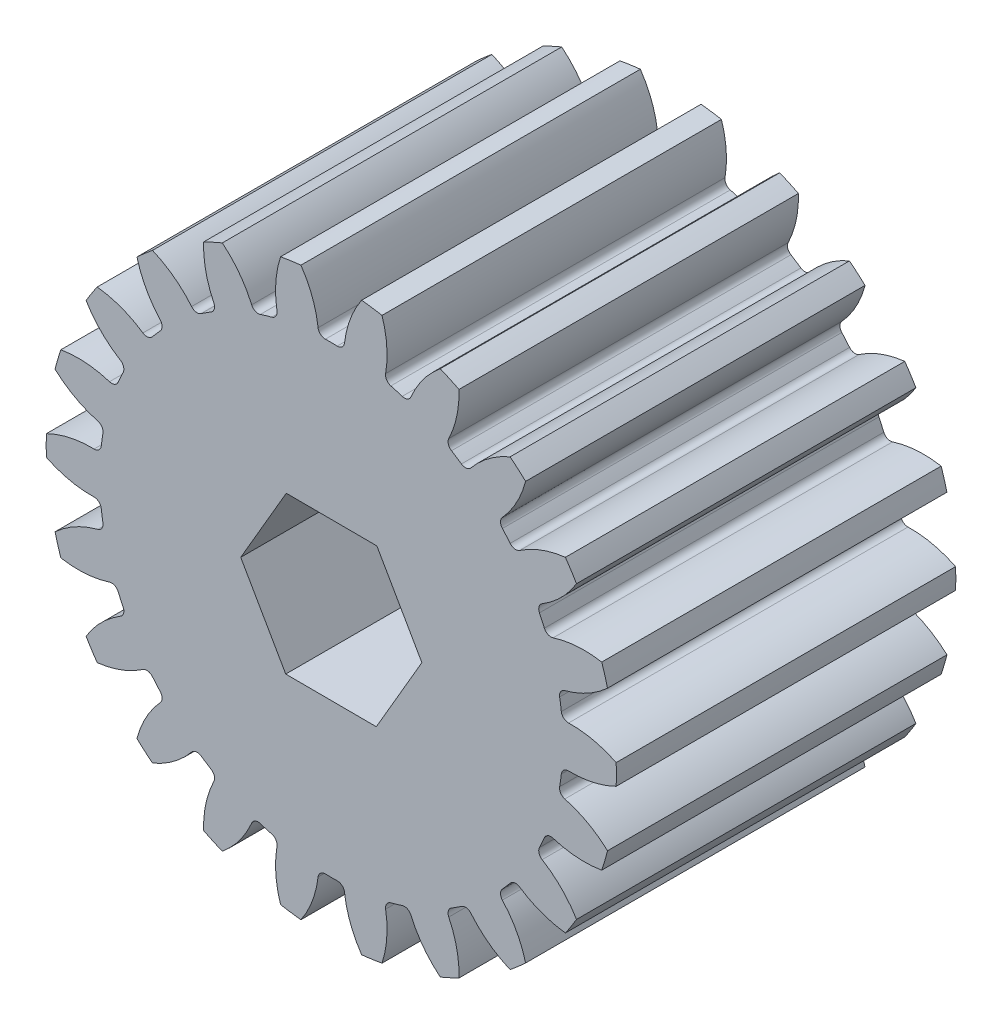
SolidWorks part; units mm, degrees
material "ABS"
ref_plane "Front Plane" through (0, 0, 0) normal (0, 0, 1) x (1, 0, 0)
ref_plane "Top Plane" through (0, 0, 0) normal (0, 1, 0) x (1, 0, 0)
ref_plane "Right Plane" through (0, 0, 0) normal (1, 0, 0) x (0, 0, -1)
sketch "Sketch1" plane through (0, 0, 0) normal (0, 0, 1) x (1, 0, 0)
  circle A0 centre (0, 0) radius 22
  circle A2 centre (0, 0) radius 24
  circle A3 centre (0, 0) radius 19.5
  dimension "D1" = 44
  dimension "D2" = 48
  dimension "D3" = 4.5
extrude "Boss-Extrude1" add sketch "Sketch1" along normal blind 25.4 and the other way blind 3.175 contours A2
sketch "Sketch3" plane through (0, 0, -3.175) normal (0, 0, -1) x (-1, 0, 0)
  line L0 (0, 0) -> (0, 24) construction
  line L1 (-1.5695, 21.9439) -> (1.5695, 21.9439) construction
  line L2 (0, 0) -> (-1.0635, 19.471) construction
  line L3 (0, 17.6319) -> (-2.6312, 24.8611) construction
  line L4 (0, 0) -> (3.4156, 23.7557) construction
  line L5 (1.5695, 21.9439) -> (4.6764, 21.4972) construction
  circle A0 centre (0, 0) radius 24 construction
  arc A1 (-3.2834, 24.7834) -> (-1.0635, 19.471) centre (-9.6529, 19.0018) cw
  arc A2 (3.2834, 24.7834) -> (1.0635, 19.471) centre (9.6529, 19.0018) ccw
  circle A3 centre (0, 0) radius 19.5 construction
  arc A4 (1.0635, 19.471) -> (-1.0635, 19.471) centre (0, 0) ccw
  arc A5 (3.2834, 24.7834) -> (-3.2834, 24.7834) centre (0, 0) ccw
  circle A6 centre (0, 0) radius 22 construction
  circle A8 centre (0, 0) radius 22 construction
  dimension "D2" = 20
  dimension "D3" = 8.182
extrude "Cut-Extrude2" cut sketch "Sketch3" against normal through all
fillet "Fillet2" radius 0.6 2 edges at (-1.0635, 19.471, 11.1125) (1.0635, 19.471, 11.1125)
pattern_circular "CirPattern2" count 22 over 360 about axis through (0, 0, -3.175) along (0, 0, 1) of "Cut-Extrude2", "Fillet2" reverse direction yes
sketch "Sketch4" plane through (0, 0, 25.4) normal (0, 0, 1) x (1, 0, 0)
  line L1 (3.8362, 6.5904) -> (-3.7894, 6.6175)
  line L2 (-3.7894, 6.6175) -> (-7.6256, 0.027)
  line L3 (-7.6256, 0.027) -> (-3.8362, -6.5904)
  line L4 (-3.8362, -6.5904) -> (3.7894, -6.6175)
  line L5 (3.7894, -6.6175) -> (7.6256, -0.027)
  line L6 (7.6256, -0.027) -> (3.8362, 6.5904)
  circle A0 centre (0, 0) radius 6.604 construction
  dimension "D1" = 13.208
extrude "Cut-Extrude3" cut sketch "Sketch4" against normal through all
sketch "Diametral Pitch (for mating)" plane through (0, 0, 25.4) normal (0, 0, 1) x (1, 0, 0)
  circle A0 centre (0, 0) radius 22
  dimension "D1" = 44
equation "\"Module\"= 2mm"
equation "\"Number of Teeth\"= 22"
equation "\"D1@Sketch1\"=\"Module\"*\"Number of Teeth\""
equation "\"D2@Sketch1\"=(\"Number of Teeth\"+2) * \"Module\""
equation "\"D3@Sketch3\"=180 /\"Number of Teeth\" "
equation "\"D1@Fillet2\"=.3 * \"Module\""
equation "\"D1@CirPattern2\"=\"Number of Teeth\""
equation "\"D3@Sketch1\"=\"Module\"*if( \"Module\"=>1.25,2.25,2.4)"
equation "\"D1@Diametral Pitch (for mating)\" = \"Module\" * \"Number of Teeth\""
